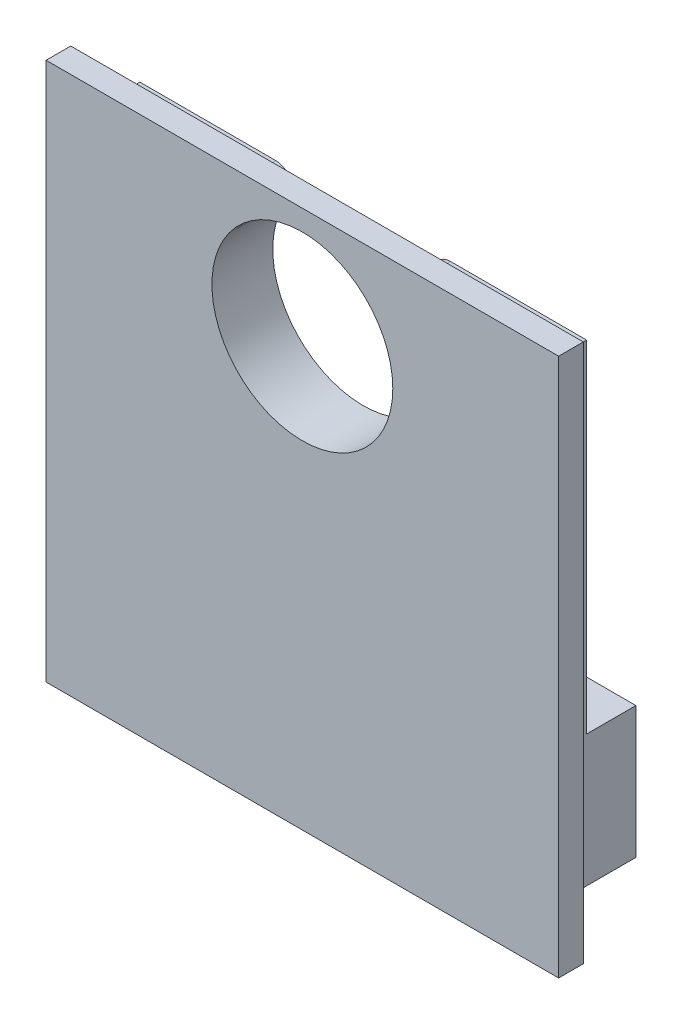
SolidWorks part; units mm, degrees
ref_plane "Front" through (0, 0, 0) normal (0, 0, 1) x (1, 0, 0)
ref_plane "Top" through (0, 0, 0) normal (0, 1, 0) x (1, 0, 0)
ref_plane "Right" through (0, 0, 0) normal (1, 0, 0) x (0, 0, -1)
sketch "Sketch1" plane through (0, 0, 0) normal (0, 0, 1) x (1, 0, 0)
  line L0 (0, 10) -> (0, -30) construction
  line L1 (13.71, -30) -> (-13.71, -30) construction
  line L2 (13.71, -30) -> (13.71, 10) construction
  line L3 (13.71, 10) -> (-13.71, 10) construction
  line L4 (-13.71, -30) -> (-13.71, 10) construction
  line L5 (13.71, -30) -> (-13.71, 10) construction
  line L6 (13.71, 10) -> (-13.71, -30) construction
  line L8 (-13.585, -24) -> (13.585, -24)
  line L9 (-13.585, -24) -> (-13.585, 4.75)
  line L10 (-13.585, 4.75) -> (13.585, 4.75)
  line L11 (13.585, -24) -> (13.585, 4.75)
  line L12 (-13.585, -24) -> (13.585, 4.75) construction
  line L13 (-13.585, 4.75) -> (13.585, -24) construction
  circle A0 centre (0, 0) radius 5.5 construction
  point P3 (0, -10)
  point P11 (0, -9.625)
  dimension "D1" = 11
  dimension "D2" = 40
  dimension "D3" = 27.42
  dimension "D4" = 10
  dimension "D5" = 28.75
  dimension "D6" = 27.17
  dimension "D7" = 6
extrude "Boss-Extrude1" add sketch "Sketch1" along normal blind 2.2
sketch "Sketch2" plane through (0, 0, 2.2) normal (0, 0, 1) x (1, 0, 0)
  line L8 (15.585, -26) -> (15.585, 6.75)
  line L9 (15.585, 6.75) -> (-15.585, 6.75)
  line L10 (-15.585, 6.75) -> (-15.585, -26)
  line L11 (-15.585, -26) -> (15.585, -26)
  line L12 (15.585, -26) -> (15.585, 6.75)
  line L13 (15.585, 6.75) -> (-15.585, 6.75)
  line L14 (-15.585, 6.75) -> (-15.585, -26)
  line L15 (-15.585, -26) -> (15.585, -26)
  dimension "D1" = 2
extrude "Boss-Extrude2" add sketch "Sketch2" along normal blind 1.5
sketch "Sketch3" plane through (0, 0, 3.7) normal (0, 0, 1) x (1, 0, 0)
  line L0 (15.585, 6.75) -> (-15.585, 6.75) construction
  line L1 (15.585, 6.75) -> (-15.585, 6.75) construction
  line L2 (-4.5666, 5.5) -> (6.9472, 5.5) construction
  circle A0 centre (0, 0) radius 5.5 construction
  circle A1 centre (0, 0) radius 5.5
  dimension "D1" = 1.25
extrude "Cut-Extrude1" cut sketch "Sketch3" against normal through all both and the other way through all
sketch "Sketch4" plane through (0, 0, 0) normal (0, 0, -1) x (-1, 0, 0)
  line L0 (13.585, 4.75) -> (13.585, -24) construction
  line L1 (-13.585, -24) -> (13.585, -24)
  line L2 (-13.585, -24) -> (-13.585, -16)
  line L3 (-13.585, -16) -> (13.585, -16)
  line L4 (13.585, -24) -> (13.585, -16)
  dimension "D1" = 8
extrude "Boss-Extrude3" add sketch "Sketch4" along normal blind 3
fillet "Fillet1" radius 1 3 edges at (0, 5.5, 2.2) (-2.7726, 4.75, 1.1) (2.7726, 4.75, 1.1)
